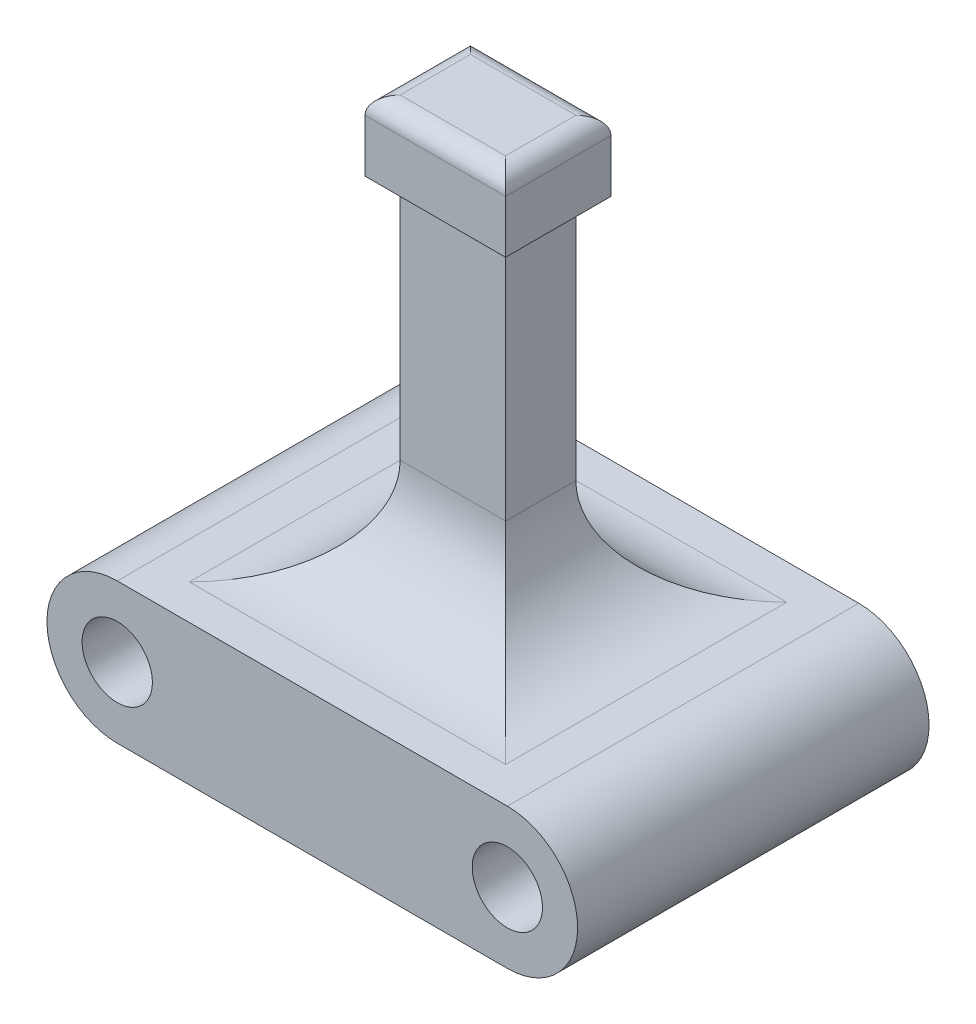
SolidWorks part; units mm, degrees
material "Rubber"
ref_plane "Front Plane" through (0, 0, 0) normal (0, 0, 1) x (1, 0, 0)
ref_plane "Top Plane" through (0, 0, 0) normal (0, 1, 0) x (1, 0, 0)
ref_plane "Right Plane" through (0, 0, 0) normal (1, 0, 0) x (0, 0, -1)
sketch "Sketch1" plane through (0, 0, 0) normal (0, 0, 1) x (1, 0, 0)
  line L0 (4.55, 0) -> (5.55, 0)
  line L1 (-4.55, 0) -> (-5.55, 0)
  line L2 (-5.55, 2) -> (5.55, 2)
  line L3 (5.55, -2) -> (-5.55, -2)
  circle A0 centre (-5.55, 0) radius 1
  circle A1 centre (5.55, 0) radius 1
  arc A2 (-5.55, 2) -> (-5.55, -2) centre (-5.55, 0) ccw
  arc A3 (5.55, -2) -> (5.55, 2) centre (5.55, 0) ccw
extrude "Boss-Extrude1" add sketch "Sketch1" along normal blind 10 contours L3 A3 L2 A2 A0 A1 region at (0, 0, 0)
sketch "Sketch2" plane through (0, 2, 0) normal (0, 1, 0) x (1, 0, 0)
  line L1 (-1.5, -4) -> (1.5, -4)
  line L2 (-1.5, -4) -> (-1.5, -6)
  line L3 (-1.5, -6) -> (1.5, -6)
  line L4 (1.5, -4) -> (1.5, -6)
  line L5 (-1.5, -4) -> (1.5, -6) construction
  line L6 (-1.5, -6) -> (1.5, -4) construction
  point P0 (0, -5)
extrude "Boss-Extrude2" add sketch "Sketch2" along normal blind 10
fillet "Fillet1" radius 3 4 edges at (0, 2, 4) (1.5, 2, 5) (0, 2, 6) (-1.5, 2, 5)
sketch "Sketch3" plane through (0, 12, 0) normal (0, 1, 0) x (1, 0, 0)
  line L1 (2, -3.5) -> (-2, -3.5)
  line L2 (2, -3.5) -> (2, -6.5)
  line L3 (2, -6.5) -> (-2, -6.5)
  line L4 (-2, -3.5) -> (-2, -6.5)
  line L5 (2, -3.5) -> (-2, -6.5) construction
  line L6 (2, -6.5) -> (-2, -3.5) construction
  point P0 (0, -5)
extrude "Boss-Extrude3" add sketch "Sketch3" along normal blind 2
fillet "Fillet2" radius 0.5 8 edges at (0, 12, 4) (1.5, 12, 5) (0, 12, 6) (-1.5, 12, 5) (0, 14, 3.5) (-2, 14, 5) (0, 14, 6.5) (2, 14, 5)
